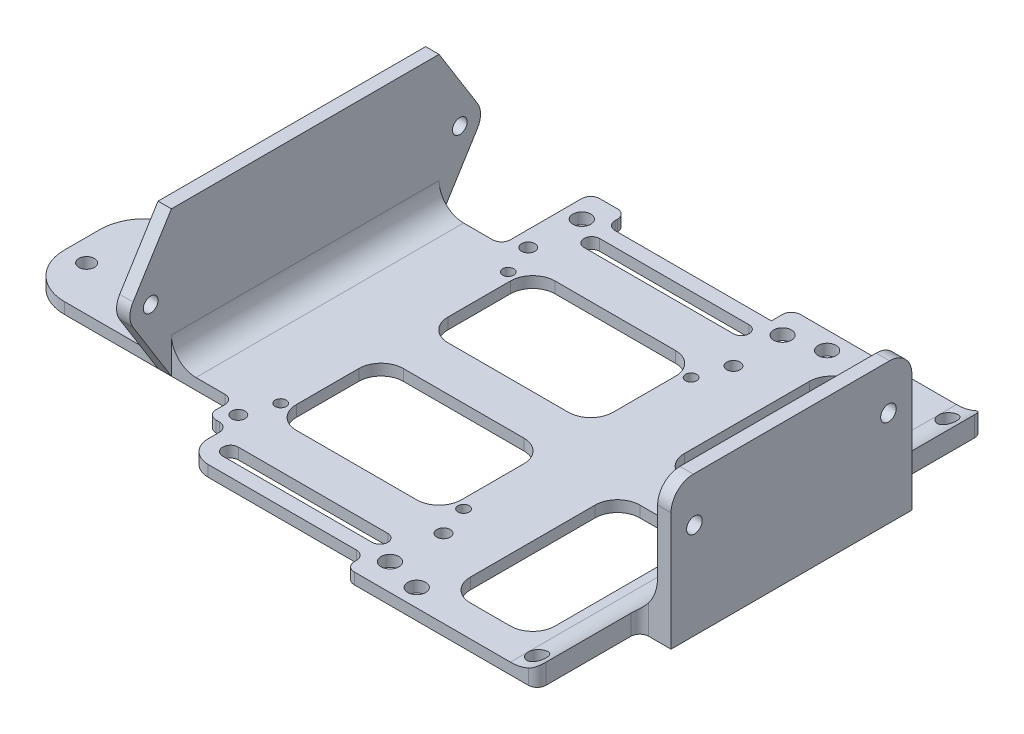
SolidWorks part; units mm, degrees
ref_plane "Front Plane" through (0, 0, 0) normal (0, 0, 1) x (1, 0, 0)
ref_plane "Top Plane" through (0, 0, 0) normal (0, 1, 0) x (1, 0, 0)
ref_plane "Right Plane" through (0, 0, 0) normal (1, 0, 0) x (0, 0, -1)
sketch "Sketch1" plane through (0, 0, 0) normal (0, 1, 0) x (1, 0, 0)
  line L0 (-70, 36) -> (68, 36) construction
  line L1 (0, 0) -> (-53, 0)
  line L2 (0, 0) -> (0, 72)
  line L3 (0, 72) -> (-53, 72)
  line L4 (-53, 0) -> (-53, 72)
  line L5 (0, 86) -> (35, 86)
  line L6 (0, 86) -> (0, -14)
  line L7 (0, -14) -> (35, -14)
  line L8 (35, 86) -> (35, -14)
  line L9 (35, 63) -> (68, 63)
  line L10 (35, 63) -> (35, 9)
  line L11 (35, 9) -> (68, 9)
  line L12 (68, 63) -> (68, 9)
  line L13 (-53, 66) -> (-70, 66)
  line L14 (-53, 66) -> (-53, 6)
  line L15 (-53, 6) -> (-70, 6)
  line L16 (-70, 66) -> (-70, 6)
  line L17 (-49.5, 68.5) -> (-3.5, 68.5) construction
  line L18 (-3.5, 68.5) -> (-3.5, 3.5) construction
  line L19 (64, 13) -> (64, 59) construction
  line L20 (48, 31) -> (55, 31)
  line L21 (13, 79) -> (22, 79)
  line L22 (8, 74) -> (8, 46)
  line L23 (13, 41) -> (22, 41)
  line L24 (27, 74) -> (27, 46)
  line L25 (-40, 65) -> (-13, 65)
  line L26 (-45, 60) -> (-45, 46)
  line L27 (-40, 41) -> (-13, 41)
  line L28 (-8, 60) -> (-8, 46)
  line L29 (48, 56) -> (55, 56)
  line L30 (43, 51) -> (43, 46)
  line L31 (48, 41) -> (55, 41)
  line L32 (60, 51) -> (60, 46)
  line L33 (60, 21) -> (60, 26)
  line L34 (48, 16) -> (55, 16)
  line L35 (43, 21) -> (43, 26)
  line L36 (13, 31) -> (22, 31)
  line L37 (27, -2) -> (27, 26)
  line L38 (13, -7) -> (22, -7)
  line L39 (8, -2) -> (8, 26)
  line L40 (-40, 31) -> (-13, 31)
  line L41 (-8, 12) -> (-8, 26)
  line L42 (-40, 7) -> (-13, 7)
  line L43 (-45, 12) -> (-45, 26)
  circle A0 centre (64, 59) radius 2
  circle A1 centre (64, 13) radius 2
  circle A2 centre (31, -10) radius 2
  circle A3 centre (4, -10) radius 2
  circle A4 centre (4, 82) radius 2
  circle A5 centre (31, 82) radius 2
  circle A6 centre (-49.5, 68.5) radius 1.5
  circle A7 centre (-3.5, 68.5) radius 1.5
  circle A8 centre (-49.5, 3.5) radius 1.5
  circle A9 centre (-3.5, 3.5) radius 1.5
  arc A10 (55, 41) -> (60, 46) centre (55, 46) ccw
  arc A11 (55, 56) -> (60, 51) centre (55, 51) cw
  arc A12 (48, 56) -> (43, 51) centre (48, 51) ccw
  arc A13 (43, 46) -> (48, 41) centre (48, 46) ccw
  arc A14 (8, 46) -> (13, 41) centre (13, 46) ccw
  arc A15 (22, 79) -> (27, 74) centre (22, 74) cw
  arc A16 (22, 41) -> (27, 46) centre (22, 46) ccw
  arc A17 (13, 79) -> (8, 74) centre (13, 74) ccw
  arc A18 (-13, 65) -> (-8, 60) centre (-13, 60) cw
  arc A19 (-13, 41) -> (-8, 46) centre (-13, 46) ccw
  arc A20 (-45, 46) -> (-40, 41) centre (-40, 46) ccw
  arc A21 (-40, 65) -> (-45, 60) centre (-40, 60) ccw
  arc A22 (55, 31) -> (60, 26) centre (55, 26) cw
  arc A23 (55, 16) -> (60, 21) centre (55, 21) ccw
  arc A24 (48, 16) -> (43, 21) centre (48, 21) cw
  arc A25 (43, 26) -> (48, 31) centre (48, 26) cw
  arc A26 (22, 31) -> (27, 26) centre (22, 26) cw
  arc A27 (22, -7) -> (27, -2) centre (22, -2) ccw
  arc A28 (8, 26) -> (13, 31) centre (13, 26) cw
  arc A29 (13, -7) -> (8, -2) centre (13, -2) cw
  arc A30 (-13, 31) -> (-8, 26) centre (-13, 26) cw
  arc A31 (-13, 7) -> (-8, 12) centre (-13, 12) ccw
  arc A32 (-45, 26) -> (-40, 31) centre (-40, 26) cw
  arc A33 (-40, 7) -> (-45, 12) centre (-40, 12) cw
  point P19 (35, 36)
  point P20 (-53, 36)
  point P39 (-26.5, 68.5)
  point P42 (-26.5, 72)
  point P43 (-3.5, 36)
  point P44 (64, 36)
  dimension "D9" = 3
  dimension "D12" = 4
  dimension "D17" = 4
  dimension "D32" = 5
  dimension "D1" = 35
  dimension "D2" = 100
  dimension "D3" = 33
  dimension "D4" = 54
  dimension "D5" = 53
  dimension "D6" = 72
  dimension "D7" = 60
  dimension "D8" = 17
  dimension "D10" = 46
  dimension "D11" = 65
  dimension "D13" = 4
  dimension "D14" = 4
  dimension "D15" = 4
  dimension "D16" = 4
  dimension "D18" = 46
  dimension "D19" = 4
  dimension "D20" = 7
  dimension "D21" = 5
  dimension "D22" = 8
  dimension "D23" = 8
  dimension "D24" = 7
  dimension "D25" = 8
  dimension "D26" = 8
  dimension "D27" = 5
  dimension "D28" = 5
  dimension "D29" = 7
  dimension "D30" = 8
  dimension "D31" = 8
extrude "Boss-Extrude1" add sketch "Sketch1" along normal blind 2.5 contours L13 L16 L15 L4 | L4 L1 L2 L3 A9 A8 A7 A6 | L8 L5 L6 L2 L7 A5 A4 A3 A2 | L12 L9 L8 L11 A1 A0
sketch "Sketch2" plane through (0, 2.5, 0) normal (0, 1, 0) x (1, 0, 0)
  line L0 (-70, 36) -> (68, 36) construction
  line L1 (-53, 66) -> (-56, 66)
  line L2 (-53, 66) -> (-53, 56)
  line L3 (-53, 56) -> (-56, 56)
  line L4 (-56, 66) -> (-56, 56)
  line L5 (-70, 66) -> (-67, 66)
  line L6 (-70, 66) -> (-70, 36)
  line L8 (-67, 66) -> (-67, 36)
  line L9 (-70, 66) -> (-70, 6) construction
  line L10 (68, 63) -> (68, 9) construction
  line L11 (-53, 66) -> (-70, 66) construction
  line L12 (-53, 16) -> (-56, 16)
  line L13 (-56, 6) -> (-56, 16)
  line L14 (-53, 6) -> (-56, 6)
  line L15 (-53, 6) -> (-53, 16)
  line L17 (-67, 6) -> (-67, 36)
  line L18 (-70, 6) -> (-67, 6)
  line L19 (-70, 6) -> (-70, 36)
  dimension "D1" = 11
  dimension "D2" = 10
extrude "Boss-Extrude2" add sketch "Sketch2" along normal blind 30
sketch "Sketch3" plane through (-70, 0, 0) normal (-1, 0, 0) x (0, 0, 1)
  line L0 (-66, 32.5) -> (-66, 0) construction
  line L1 (-66, 32.5) -> (-74.5961, 18.7098)
  line L2 (-66, 0) -> (-74.5961, 13.7902)
  line L3 (-66, 32.5) -> (-66, 0)
  line L4 (-36, 32.5) -> (-36, 0) construction
  line L5 (-66, 32.5) -> (-6, 32.5) construction
  line L6 (-66, 0) -> (-6, 0) construction
  line L7 (-6, 32.5) -> (-6, 0)
  line L8 (-6, 0) -> (2.5961, 13.7902)
  line L9 (-6, 32.5) -> (2.5961, 18.7098)
  circle A0 centre (-70.65, 16.25) radius 1.65
  arc A2 (-74.5961, 18.7098) -> (-74.5961, 13.7902) centre (-70.65, 16.25) ccw
  circle A3 centre (-70.65, 16.25) radius 4.65 construction
  arc A4 (2.5961, 18.7098) -> (2.5961, 13.7902) centre (-1.35, 16.25) cw
  circle A5 centre (-1.35, 16.25) radius 1.65
  dimension "D1" = 3.3
  dimension "D3" = 3
extrude "Boss-Extrude3" add sketch "Sketch3" against normal up to surface (3 mm away) up to face at (-67, 17.5, -36)
fillet "Fillet2" radius 10 2 edges at (-54.5, 2.5, -56) (-54.5, 2.5, -16)
fillet "Fillet3" radius 5.5 3 edges at (-56, 2.5, -16) (-56, 2.5, -56) (-67, 2.5, -36)
sketch "Sketch4" plane through (0, 0, 0) normal (0, -1, 0) x (1, 0, 0)
  line L0 (-67, -66) -> (-70, -66) construction
  line L1 (-70, -6) -> (-110, -6)
  line L2 (-70, -6) -> (-70, -66)
  line L3 (-70, -66) -> (-110, -66)
  line L4 (-110, -6) -> (-110, -66)
  circle A0 centre (-106, -10) radius 2
  circle A1 centre (-76, -10) radius 2
  circle A2 centre (-106, -36) radius 2
  circle A3 centre (-106, -62) radius 2
  circle A4 centre (-76, -36) radius 2
  circle A5 centre (-76, -62) radius 2
  point P25 (-110, -36)
  dimension "D2" = 4
  dimension "D1" = 40
  dimension "D3" = 6
  dimension "D4" = 4
  dimension "D5" = 4
  dimension "D6" = 4
extrude "Boss-Extrude4" add sketch "Sketch4" against normal up to surface (2.5 mm away) up to face at (-26.5, 2.5, -53)
sketch "Sketch5" plane through (0, 2.5, 0) normal (0, 1, 0) x (1, 0, 0)
  line L0 (0, 0) -> (-53, 0) construction
  line L1 (-53, 72) -> (0, 72)
  line L2 (-53, 72) -> (-53, 86)
  line L3 (-53, 86) -> (-45, 86)
  line L4 (0, 72) -> (0, 86)
  line L5 (0, -14) -> (-8, -14)
  line L6 (0, -14) -> (0, 0)
  line L7 (0, 0) -> (-8, 0)
  line L8 (-8, -14) -> (-8, 0)
  line L9 (-8, 86) -> (0, 86)
  line L11 (-45, 86) -> (-45, 72)
  line L12 (-45, 72) -> (-8, 72)
  line L13 (-8, 86) -> (-8, 72)
  circle A0 centre (-4, 80) radius 2
  circle A1 centre (-49, 80) radius 2
  circle A2 centre (-4, -8) radius 2
  dimension "D1" = 4
  dimension "D2" = 4
  dimension "D3" = 4
  dimension "D4" = 8
  dimension "D5" = 8
  dimension "D6" = 4
  dimension "D7" = 4
  dimension "D8" = 4
extrude "Boss-Extrude5" add sketch "Sketch5" along direction (0, 1, 0) on the side against the normal blind 2.5 contours L11 L3 L2 L1 A1 | L9 L13 L1 L4 A0 | L8 L5 L6 L7 A2
sketch "Sketch6" plane through (0, 2.5, 0) normal (0, 1, 0) x (1, 0, 0)
  line L0 (-43.25, 76.5) -> (-9.75, 76.5) construction
  line L1 (-43.25, 78.25) -> (-9.75, 78.25)
  line L2 (-43.25, 74.75) -> (-9.75, 74.75)
  line L3 (-43.25, -4.5) -> (-9.75, -4.5) construction
  line L4 (-43.25, -2.75) -> (-9.75, -2.75)
  line L5 (-43.25, -6.25) -> (-9.75, -6.25)
  line L6 (-45, 86) -> (-45, 72) construction
  line L9 (-8, -14) -> (-8, 0) construction
  line L10 (-43.25, -4.5) -> (-43.25, 0) construction
  line L11 (-8, 0) -> (-53, 0) construction
  line L12 (-26.5, 76.5) -> (-26.5, 72) construction
  line L13 (-8, 72) -> (-45, 72) construction
  line L14 (-45, 81.5) -> (-8, 81.5)
  line L15 (-8, 86) -> (-8, 72) construction
  line L16 (-8, 81.5) -> (-8, 72)
  line L17 (-8, 72) -> (-45, 72)
  line L18 (-45, 81.5) -> (-45, 72)
  line L20 (-8, -9.5) -> (-48.25, -9.5)
  line L21 (-8, -9.5) -> (-8, 0)
  line L22 (-8, 0) -> (-48.25, 0)
  line L23 (-48.25, -9.5) -> (-48.25, 0)
  arc A0 (-43.25, 78.25) -> (-43.25, 74.75) centre (-43.25, 76.5) ccw
  arc A1 (-9.75, 74.75) -> (-9.75, 78.25) centre (-9.75, 76.5) ccw
  arc A2 (-43.25, -2.75) -> (-43.25, -6.25) centre (-43.25, -4.5) ccw
  arc A3 (-9.75, -6.25) -> (-9.75, -2.75) centre (-9.75, -4.5) ccw
  point P2 (-26.5, 76.5)
  point P7 (-26.5, -4.5)
  dimension "D1" = 1.75
  dimension "D2" = 81
  dimension "D3" = 5
  dimension "D4" = 5
  dimension "D5" = 5
extrude "Boss-Extrude6" add sketch "Sketch6" against normal up to surface (2.5 mm away) contours A1 L2 A0 L18 L17 L16 | A1 L16 L14 L18 A0 L1 | L5 A3 L4 A2 | L21 L20 L23 L22 up to face at (-25.0909, 0, -40.5455)
sketch "Sketch7" plane through (0, 2.5, 0) normal (0, 1, 0) x (1, 0, 0)
  line L2 (-9.75, -2.75) -> (-43.25, -2.75)
  line L3 (-43.25, -6.25) -> (-9.75, -6.25)
  line L4 (-9.75, -2.75) -> (-43.25, -2.75)
  line L5 (-43.25, -6.25) -> (-9.75, -6.25)
  line L6 (-9.75, 78.25) -> (-43.25, 78.25)
  line L7 (-43.25, 74.75) -> (-9.75, 74.75)
  line L8 (-9.75, 78.25) -> (-43.25, 78.25)
  line L9 (-43.25, 74.75) -> (-9.75, 74.75)
  line L12 (-48.25, -9.5) -> (-8, -9.5)
  line L13 (-8, -9.5) -> (-8, 0)
  line L14 (-8, 0) -> (-48.25, 0)
  line L15 (-48.25, 0) -> (-48.25, -9.5)
  line L16 (-48.25, -9.5) -> (-8, -9.5)
  line L17 (-8, -9.5) -> (-8, 0)
  line L18 (-8, 0) -> (-48.25, 0)
  line L19 (-48.25, 0) -> (-48.25, -9.5)
  line L20 (-8, 81.5) -> (-45, 81.5)
  line L21 (-8, 72) -> (-8, 81.5)
  line L22 (-45, 72) -> (-8, 72)
  line L23 (-45, 81.5) -> (-45, 72)
  line L24 (-8, 81.5) -> (-45, 81.5)
  line L25 (-8, 72) -> (-8, 81.5)
  line L26 (-45, 72) -> (-8, 72)
  line L27 (-45, 81.5) -> (-45, 72)
  arc A2 (-9.75, -6.25) -> (-9.75, -2.75) centre (-9.75, -4.5) ccw
  arc A3 (-43.25, -2.75) -> (-43.25, -6.25) centre (-43.25, -4.5) ccw
  arc A4 (-9.75, -6.25) -> (-9.75, -2.75) centre (-9.75, -4.5) ccw
  arc A5 (-43.25, -2.75) -> (-43.25, -6.25) centre (-43.25, -4.5) ccw
  arc A6 (-9.75, 74.75) -> (-9.75, 78.25) centre (-9.75, 76.5) ccw
  arc A7 (-43.25, 78.25) -> (-43.25, 74.75) centre (-43.25, 76.5) ccw
  arc A8 (-9.75, 74.75) -> (-9.75, 78.25) centre (-9.75, 76.5) ccw
  arc A9 (-43.25, 78.25) -> (-43.25, 74.75) centre (-43.25, 76.5) ccw
  dimension "D1" = 0
  dimension "D2" = 0
  dimension "D3" = 0
  dimension "D4" = 0
extrude "Cut-Extrude1" cut sketch "Sketch7" against normal through all contours L4 A5 L5 A4
fillet "Fillet4" radius 5 1 edges at (-48.25, 1.25, 9.5)
fillet "Fillet5" radius 2 18 edges at (-110, 1.25, -6) (-110, 1.25, -66) (-53, 1.25, -66) (-53, 1.25, -6) (-53, 1.25, 0) (-48.25, 1.25, 0) (-8, 1.25, 9.5) (-8, 1.25, 14) (35, 1.25, 14) (35, 1.25, -9) (68, 1.25, -9) (68, 1.25, -63) (35, 1.25, -63) (35, 1.25, -86) (-8, 1.25, -86) (-45, 1.25, -81.5) (-45, 1.25, -86) (-53, 1.25, -86)
sketch "Sketch8" plane through (0, 2.5, 0) normal (0, 1, 0) x (1, 0, 0)
  line L0 (37, 63) -> (66, 63) construction
  line L1 (39, 63) -> (42, 63)
  line L2 (39, 63) -> (39, 9)
  line L3 (39, 9) -> (42, 9)
  line L4 (42, 63) -> (42, 9)
  line L5 (37, 9) -> (66, 9) construction
  line L6 (68, 61) -> (68, 11) construction
  dimension "D1" = 3
  dimension "D2" = 26
extrude "Boss-Extrude7" add sketch "Sketch8" along normal blind 29
fillet "Fillet6" [suppressed] radius 5
sketch "Sketch9" plane through (42, 0, 0) normal (1, 0, 0) x (0, 0, -1)
  line L0 (9, 31.5) -> (63, 31.5) construction
  line L1 (14.25, 21.5) -> (9, 21.5)
  line L2 (9, 31.5) -> (9, 2.5) construction
  line L3 (57.75, 21.5) -> (63, 21.5)
  line L4 (63, 31.5) -> (63, 2.5) construction
  circle A0 centre (14.25, 21.5) radius 1.75
  circle A1 centre (57.75, 21.5) radius 1.75
  dimension "D3" = 3.5
  dimension "D1" = 43.5
  dimension "D2" = 10
extrude "Cut-Extrude2" cut sketch "Sketch9" against normal up to surface (3 mm away) up to face at (39, 17, -36)
fillet "Fillet7" radius 5 2 edges at (40.5, 31.5, -63) (40.5, 31.5, -9)
sketch "Sketch10" plane through (0, 2.5, 0) normal (0, 1, 0) x (1, 0, 0)
  line L0 (-70, 6) -> (-108, 6) construction
  line L1 (-47, 10.5) -> (-6, 10.5) construction
  line L2 (-6, 10.5) -> (-6, 61.5) construction
  line L3 (-26.5, 7) -> (-26.5, 10.5) construction
  line L4 (-40, 7) -> (-13, 7) construction
  line L5 (-26.5, 41) -> (-26.5, 31) construction
  line L6 (-40, 41) -> (-13, 41) construction
  line L7 (-40, 31) -> (-13, 31) construction
  line L8 (-26.5, 31) -> (-26.5, 36) construction
  line L9 (-26.5, 36) -> (-6, 36) construction
  line L10 (-70, 66) -> (-70, 6) construction
  line L11 (-101, 6) -> (-101, 34)
  line L12 (-101, 34) -> (-70, 34)
  line L15 (-110, 64) -> (-110, 8)
  line L16 (-108, 6) -> (-70, 6)
  line L17 (-70, 6) -> (-70, 66)
  line L18 (-70, 66) -> (-108, 66)
  line L19 (-110, 64) -> (-110, 8)
  line L20 (-108, 6) -> (-101, 6)
  line L21 (-70, 34) -> (-70, 66)
  line L22 (-70, 66) -> (-108, 66)
  circle A0 centre (-47, 61.5) radius 1.25
  circle A1 centre (-47, 10.5) radius 1.25
  circle A2 centre (-6, 10.5) radius 1.25
  circle A3 centre (-6, 61.5) radius 1.25
  circle A4 centre (-96, 16) radius 1.75
  circle A5 centre (-78, 16) radius 1.75
  circle A6 centre (-76, 36) radius 2 construction
  arc A8 (-110, 8) -> (-108, 6) centre (-108, 8) ccw
  arc A9 (-108, 66) -> (-110, 64) centre (-108, 64) ccw
  arc A10 (-110, 8) -> (-108, 6) centre (-108, 8) ccw
  arc A11 (-108, 66) -> (-110, 64) centre (-108, 64) ccw
  dimension "D2" = 2.5
  dimension "D5" = 3.5
  dimension "D1" = 41
  dimension "D3" = 51
  dimension "D4" = 18
  dimension "D6" = 10
  dimension "D7" = 8
  dimension "D9" = 5
  dimension "D8" = 0
extrude "Cut-Extrude3" cut sketch "Sketch10" against normal through all
fillet "Fillet8" radius 10 3 edges at (-70, 1.25, -34) (-101, 1.25, -6) (-101, 1.25, -34)
sketch "Sketch11" plane through (0, 2.5, 0) normal (0, 1, 0) x (1, 0, 0)
  line L1 (-61.5, 66) -> (-53, 66)
  line L2 (-61.5, 66) -> (-61.5, 6)
  line L3 (-61.5, 6) -> (-53, 6)
  line L4 (-53, 66) -> (-53, 6)
extrude "Cut-Extrude4" cut sketch "Sketch11" along normal through all
sketch "Sketch12" plane through (0, 2.5, 0) normal (0, 1, 0) x (1, 0, 0)
  line L4 (66, 63) -> (42, 63)
  line L5 (42, 63) -> (42, 9)
  line L6 (42, 9) -> (66, 9)
  line L7 (68, 11) -> (68, 61)
  line L8 (66, 63) -> (42, 63)
  line L9 (42, 63) -> (42, 9)
  line L10 (42, 9) -> (66, 9)
  line L11 (68, 11) -> (68, 61)
  arc A2 (66, 9) -> (68, 11) centre (66, 11) ccw
  arc A3 (68, 61) -> (66, 63) centre (66, 61) ccw
  arc A4 (66, 9) -> (68, 11) centre (66, 11) ccw
  arc A5 (68, 61) -> (66, 63) centre (66, 61) ccw
  dimension "D1" = 0
extrude "Cut-Extrude5" cut sketch "Sketch12" against normal through all
fillet "Fillet9" radius 10 1 edges at (39, 2.5, -36)
